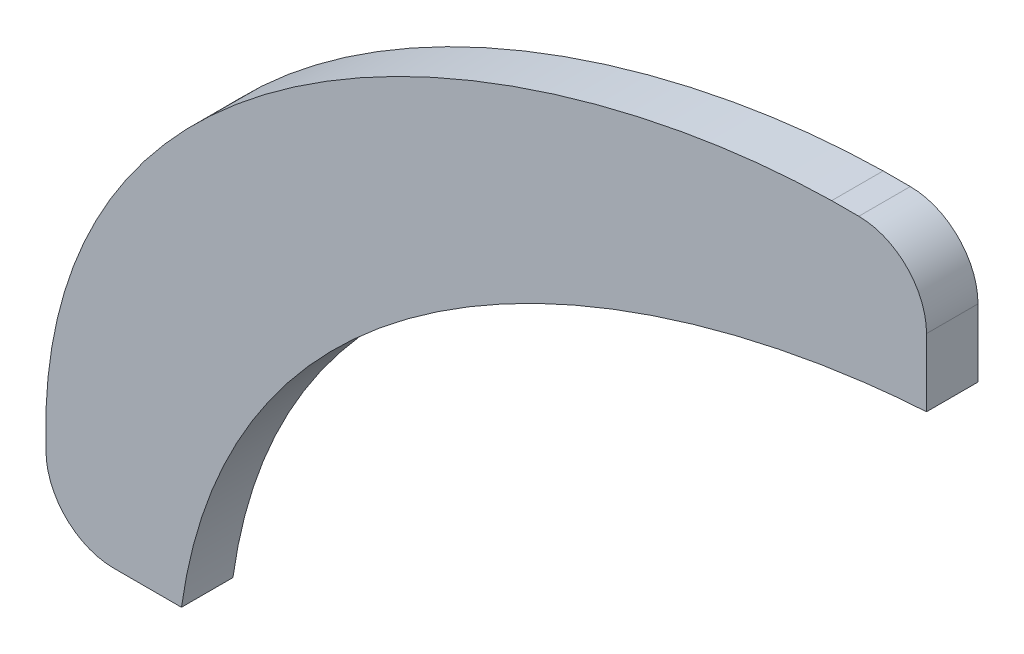
SolidWorks part; units mm, degrees
ref_plane "Front Plane" through (0, 0, 0) normal (0, 0, 1) x (1, 0, 0)
ref_plane "Top Plane" through (0, 0, 0) normal (0, 1, 0) x (1, 0, 0)
ref_plane "Right Plane" through (0, 0, 0) normal (1, 0, 0) x (0, 0, -1)
sketch "Sketch1" plane through (0, 0, 0) normal (0, 0, 1) x (1, 0, 0)
  line L1 (6.35, 0) -> (82.55, 0)
  line L2 (0, 6.35) -> (0, 63.5)
  line L3 (0, 63.5) -> (76.2, 63.5)
  line L4 (82.55, 0) -> (82.55, 57.15)
  arc A0 (82.55, 57.15) -> (76.2, 63.5) centre (76.2, 57.15) ccw
  arc A1 (0, 6.35) -> (6.35, 0) centre (6.35, 6.35) ccw
  spline S0 degree 3 poles (0, 6.35) (-1.4343, 43.9963) (45.0346, 64.052) (76.2, 63.5) knots 0 0 0 0 1 1 1 1
  spline S1 degree 3 poles (12.7, 0) (17.2635, 32.9464) (53.3334, 49.0332) (82.55, 50.8) knots 0 0 0 0 1 1 1 1
  point P7 (82.55, 63.5)
  point P10 (0, 0)
  dimension "D3" = 6.35
  dimension "D4" = 12.7
  dimension "D1" = 82.55
  dimension "D2" = 63.5
  dimension "D5" = 12.7
extrude "Boss-Extrude1" add sketch "Sketch1" along normal blind 4.826 contours L1 S1 L4 A0 L3 S0 L2 A1 region at (34.6367, 38.2503, 0)
equation "\"MDF\"= 0.19in"
equation "\"PVCID\" = 2.067in"
equation "\"PVCOD\" = 2.375in"
equation "\"GenDiameter\"= 60mm"
equation "\"GenCutDiameter\" = 1.8in"
equation "\"GenCutDistance\" = 1"
equation "\"TowerHeight\" = 6in"
equation "\"TowerFrontBase\" = 3in"
equation "\"FunnelHeight\" = 1in"
equation "\"FunnelAngle\" = 20"
equation "\"TowerSideBase\" = 3in"
equation "\"TowerPanelLength\" = 2in"
equation "\"TowerPanelLeeway\" = 0.5in"
equation "\"BaseLength\" = 9in"
equation "\"BaseWidth\" = 10in"
equation "\"WheelHoleLength\" = 3.25in"
equation "\"WheelHoleWidth\" = 26mm"
equation "\"WheelHoleFromBack\" = 1in"
equation "\"DropLength\" = 1in"
equation "\"DropWidth\" = 8.5in"
equation "\"BumperWidth\" = 1in"
equation "\"SmallHexDiameter\" = 0.185in"
equation "\"SmallHexHeight\" = 0.701in"
equation "\"ScrewSize\" = 0.106in"
equation "\"BigHexDiameter\" = 0.251in"
equation "\"BigHexHeight\" = 0.374in"
equation "\"PCBThickness\" = 0.066in"
equation "\"ConnectorHeight\" = 0.517in"
equation "\"BoardHeight\" = 0.583in"
equation "\"UnoStackHeight\" = 1.351in"
equation "\"UnoStackWidth\" = 3.053in"
equation "\"UnoStackLength\" = 3.152in"
equation "\"HBridgeWidth\" = 1.797in"
equation "\"HBridgeLength\" = 2.236in"
equation "\"DSWidth\" = 1.820in"
equation "\"DSLength\" = 1.833in"
equation "\"StepperWidth\" = 1.799in"
equation "\"StepperLength\" = 2.248in"
equation "\"ULNWidth\" = 1.304in"
equation "\"ULNLength\" = 1.545in"
equation "\"VSwitchHeight\" = 0.392in"
equation "\"VSwitchWidth\" = 0.637in"
equation "\"VSwitchLength\" = 1.097in"
equation "\"SkateWheelDiameter\" = 80mm"
equation "\"SkateWheelThickness\" = 24mm"
equation "\"BaseDistance\" = 3in"
equation "\"DummyVar\" = 2in"
equation "\"D1@Boss-Extrude1\"=\"MDF\""
